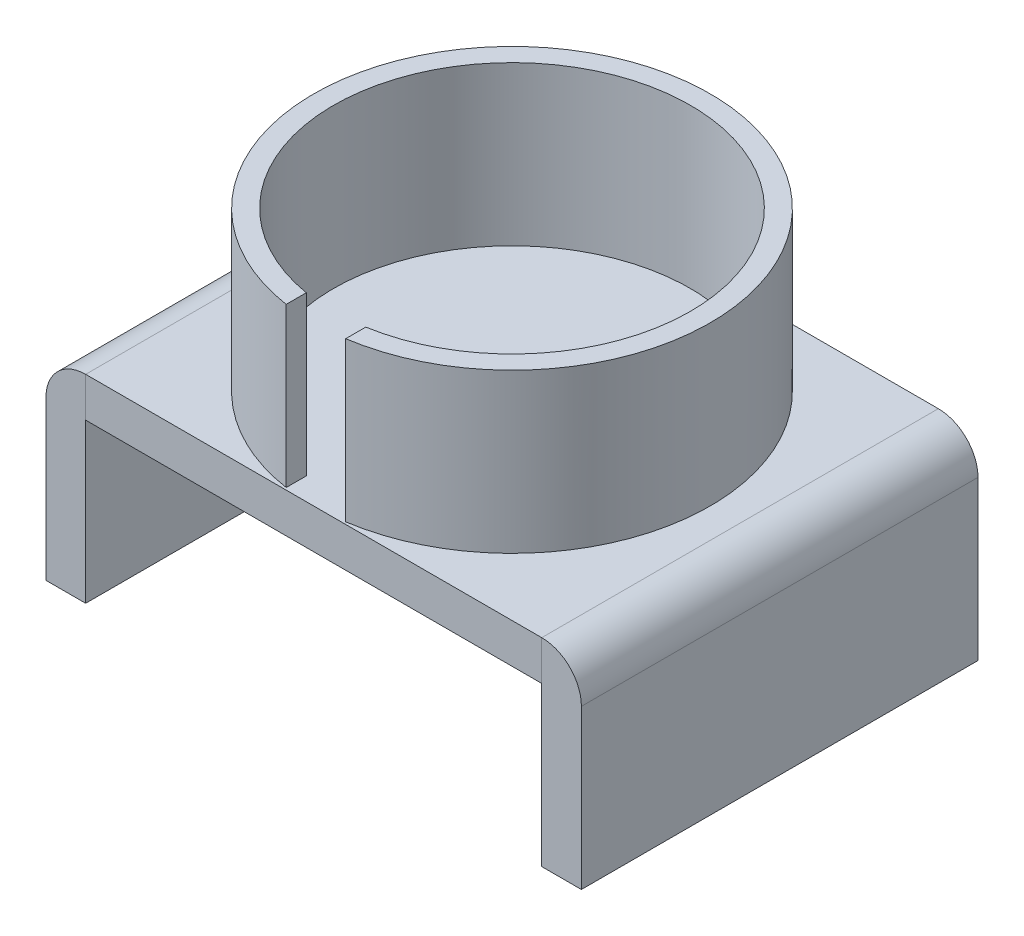
SolidWorks part; units mm, degrees
ref_plane "Plan de face" through (0, 0, 0) normal (0, 0, 1) x (1, 0, 0)
ref_plane "Plan de dessus" through (0, 0, 0) normal (0, 1, 0) x (1, 0, 0)
ref_plane "Plan de droite" through (0, 0, 0) normal (1, 0, 0) x (0, 0, -1)
sketch "socle" plane through (0, 0, 0) normal (0, 1, 0) x (1, 0, 0)
  line L1 (-58.308, 62.2951) -> (56.692, 62.2951)
  line L2 (-58.308, 62.2951) -> (-58.308, -37.7049)
  line L3 (-58.308, -37.7049) -> (56.692, -37.7049)
  line L4 (56.692, 62.2951) -> (56.692, -37.7049)
  dimension "D1" = 115
  dimension "D2" = 100
extrude "extrusion du socle" add sketch "socle" along normal blind 10
sketch "fixations latérales" plane through (0, 0, 0) normal (0, -1, 0) x (1, 0, 0)
  line L0 (-0.808, 37.7049) -> (-0.808, -84.4135) construction
  line L2 (-58.308, -62.2951) -> (-68.308, -62.2951)
  line L3 (56.692, 37.7049) -> (66.692, 37.7049)
  line L4 (56.692, 37.7049) -> (56.692, -62.2951)
  line L5 (56.692, -62.2951) -> (66.692, -62.2951)
  line L6 (66.692, 37.7049) -> (66.692, -62.2951)
  line L7 (-68.308, 37.7049) -> (-68.308, -62.2951)
  line L8 (-58.308, 37.7049) -> (-68.308, 37.7049)
  line L9 (-58.308, 37.7049) -> (-58.308, -62.2951)
  dimension "D1" = 10
extrude "extrusion des fixations latérales" add sketch "fixations latérales" along normal blind 40 and the other way blind 10 separate body
fillet "congé fixation gauche" radius 10 1 edges at (-68.308, 10, -12.2951) type face fillet first side face at (-68.308, -15, -12.2951) second side face at (-63.308, 10, -12.2951)
fillet "congé fixation droite" radius 10 1 edges at (66.692, 10, -12.2951) type face fillet first side face at (61.692, 10, -12.2951) second side face at (66.692, -15, -12.2951)
sketch "socle tasse" plane through (0, 10, 0) normal (0, 1, 0) x (1, 0, 0)
  line L0 (-58.308, 62.2951) -> (56.692, -37.7049) construction
  line L1 (56.692, 62.2951) -> (-58.308, -37.7049) construction
  line L2 (-0.808, 12.2951) -> (-0.808, -37.7049) construction
  line L3 (-8.308, -37.1392) -> (-8.308, -32.0755)
  line L4 (-8.308, -41.6034) -> (-8.308, -23.8064) construction
  line L5 (6.692, -42.8279) -> (6.692, -22.5819) construction
  line L6 (6.692, -31.7789) -> (6.692, -37.1392)
  arc A0 (6.692, -32.0755) -> (-8.308, -32.0755) centre (-0.808, 12.2951) ccw
  arc A1 (6.692, -37.1392) -> (-8.308, -37.1392) centre (-0.808, 12.2951) ccw
  point P15 (-0.808, -32.7049)
  point P18 (-8.308, -32.7049)
  point P21 (6.692, -32.7049)
extrude "extrusion fixation tasse" add sketch "socle tasse" along normal blind 40 contours L6 A1 L3 A0 region at (-0.808, 10, -60.8849)
